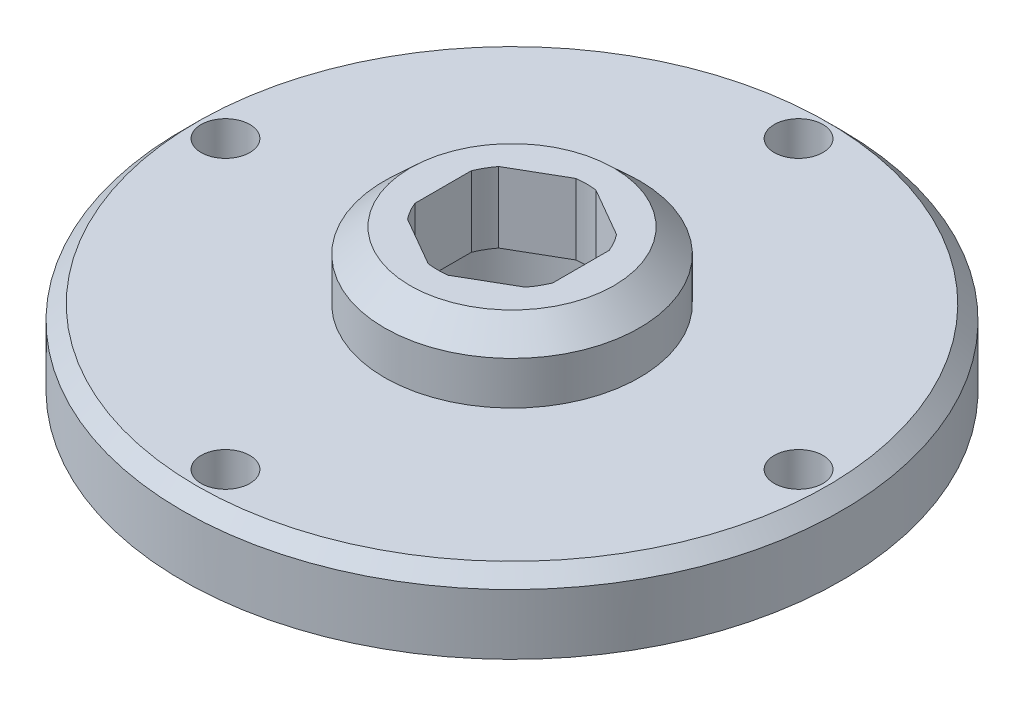
SolidWorks part; units mm, degrees
material "Nylon 6/10"
ref_plane "Front Plane" through (0, 0, 0) normal (0, 0, 1) x (1, 0, 0)
ref_plane "Top Plane" through (0, 0, 0) normal (0, 1, 0) x (1, 0, 0)
ref_plane "Right Plane" through (0, 0, 0) normal (1, 0, 0) x (0, 0, -1)
sketch "Sketch1" plane through (0, 0, 0) normal (0, 0, 1) x (1, 0, 0)
  line L0 (6.8, 0) -> (6.8, 4.953)
  line L1 (6.8, 4.953) -> (5.2, 4.953)
  line L2 (5.2, 4.953) -> (5.2, 9.8823)
  line L3 (5.2, 9.8823) -> (7.112, 9.8823)
  line L5 (8.9, 5.2198) -> (23, 5.2198)
  line L6 (23, 5.2198) -> (23, 0)
  line L7 (23, 0) -> (6.8, 0)
  line L8 (7.112, 9.8823) -> (8.9, 8.2198)
  line L9 (8.9, 8.2198) -> (8.9, 5.2198)
  line L10 (0, 0) -> (0, 16.4092) construction
  dimension "D1" = 6.8
  dimension "D2" = 23
  dimension "D3" = 4.953
  dimension "D4" = 8.9
  dimension "D5" = 4.6625
  dimension "D6" = 5.2198
  dimension "D7" = 3
  dimension "D8" = 7.112
  dimension "D9" = 5.2
revolve "Revolve1" add sketch "Sketch1" angle 360 about L10
sketch "Sketch2" plane through (0, 0, 0) normal (0, 1, 0) x (1, 0, 0)
  circle A0 centre (0, 0) radius 20 construction
  point P3 (-20, 0)
  dimension "D1" = 40
hole_wizard "M3 Clearance Hole1" positions "Sketch2" profile "Sketch3" hole size "M3" standard "ANSI Metric" end condition through all
sketch "Sketch3" plane through (-20, 0, 0) normal (1, 0, 0) x (0, 0, -1)
  line L0 (0, 0) -> (0, 9.8823)
  line L1 (0, 9.8823) -> (1.7, 9.8823)
  line L2 (1.7, 9.8823) -> (1.7, 0)
  line L5 (1.7, 0) -> (0, 0)
  line L11 (0, -6.35) -> (0, 107.95) construction
  dimension "Thru Hole Dia." = 3.4
  dimension "Thru Hole Depth" = 9.8823
pattern_circular "CirPattern1" count 4 over 360 about axis through (0, 0, 0) along (0, -1, 0) of "M3 Clearance Hole1"
sketch "Sketch4" plane through (0, 4.953, 0) normal (0, -1, 0) x (1, 0, 0)
  line L1 (4.8125, 2.7785) -> (0, 5.557)
  line L2 (0, 5.557) -> (-4.8125, 2.7785)
  line L3 (-4.8125, 2.7785) -> (-4.8125, -2.7785)
  line L4 (-4.8125, -2.7785) -> (0, -5.557)
  line L5 (0, -5.557) -> (4.8125, -2.7785)
  line L6 (4.8125, -2.7785) -> (4.8125, 2.7785)
  circle A0 centre (0, 0) radius 4.8125 construction
  circle A1 centre (0, 0) radius 5.2 construction
  circle A2 centre (0, 0) radius 5.2
  circle M9 centre (0, 0) radius 5.2
  dimension "D1" = 9.625
extrude "Boss-Extrude1" add sketch "Sketch4" against normal up to surface (4.9293 mm away) contours L2 M9 | L3 M9 | L4 M9 | L5 M9 | L6 M9 | L1 M9 region at (2.484, 4.953, 4.3024) region at (4.968, 4.953, 0) region at (-2.484, 4.953, 4.3024) region at (2.484, 4.953, -4.3024) region at (-4.968, 4.953, 0) region at (-2.484, 4.953, -4.3024) up to face at (0, 9.8823, -5.2)
chamfer "Chamfer1" distance 0.75 angle 45 1 edges at (0, 0, -6.8)
chamfer "Chamfer2" distance 1 angle 45 1 edges at (0, 5.2198, -23)
